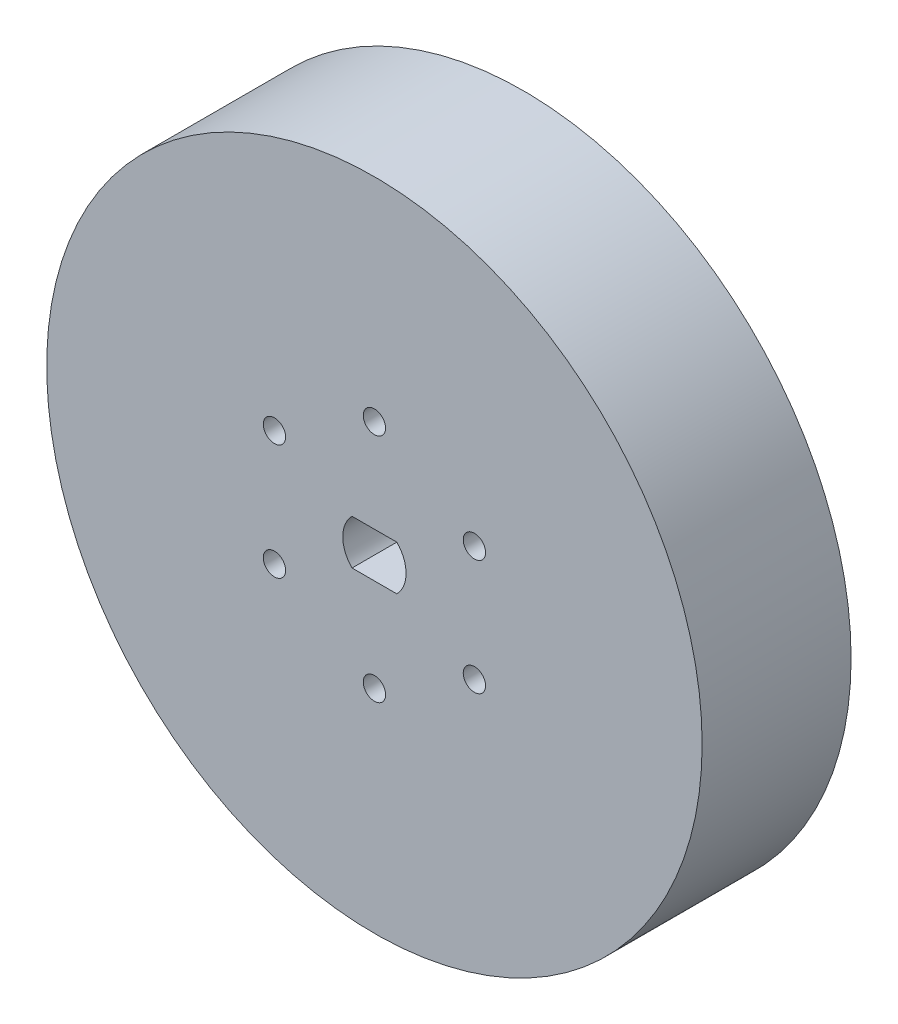
SolidWorks part; units mm, degrees
ref_plane "Front Plane" through (0, 0, 0) normal (0, 0, 1) x (1, 0, 0)
ref_plane "Top Plane" through (0, 0, 0) normal (0, 1, 0) x (1, 0, 0)
ref_plane "Right Plane" through (0, 0, 0) normal (1, 0, 0) x (0, 0, -1)
sketch "Sketch1" plane through (0, 0, 0) normal (0, 0, 1) x (1, 0, 0)
  line L0 (-39.5653, 22.858) -> (-42.5705, 19.8528) construction
  line L7 (-42.5705, 19.8528) -> (-45.5757, 22.858) construction
  line L8 (-39.5653, 22.858) -> (-45.5757, 22.858)
  line L9 (-42.5705, 19.8528) -> (-42.5705, 25.8632) construction
  line L10 (-45.5757, 28.8684) -> (-39.5653, 28.8684)
  line L11 (-42.5705, 28.8684) -> (-42.5705, 30.1132) construction
  circle A0 centre (-42.5705, 25.8632) radius 44
  circle A1 centre (-42.5705, 25.8632) radius 4.25
  dimension "D1" = 45
  dimension "D2" = 1.2448
  dimension "WheelOD" = 88
  dimension "ShaftMajorDiameter" = 8.5
extrude "Boss-Extrude1" add sketch "Sketch1" along normal blind 20 contours A0 A1 | L10 A1 | L8 A1 region at (-42.5705, 22.3532, 0) region at (-42.5705, 29.3732, 0) region at (-85.326, 25.8632, 0)
ref_plane "Plane1" through (0, 0, 0) normal (0, 0, -1) x (-1, 0, 0)
sketch "Sketch2" plane through (0, 0, 0) normal (0, 0, -1) x (-1, 0, 0)
  circle A0 centre (42.5705, 41.3632) radius 3
  circle A1 centre (42.5705, 41.3632) radius 1.5
  point P3 (0, 0)
  dimension "D1" = 6
  dimension "D2" = 3
  dimension "D3" = 15.5
extrude "Cut-Extrude1" cut sketch "Sketch2" against normal through all contours A1
extrude "Cut-Extrude2" cut sketch "Sketch2<3>" against normal blind 3 contours A0
sketch "Sketch2<3>" plane through (0, 0, 0) normal (0, 0, -1) x (-1, 0, 0) same geometry as "Sketch2"
ref_plane "Plane2" through (0, 0, 10) normal (0, 0, -1) x (-1, 0, 0)
pattern_circular "CirPattern1" count 6 over 360 about axis through (-42.5705, 25.8632, 20) along (0, 0, 1) of "Cut-Extrude1", "Cut-Extrude2"
equation "\"WheelOD\"= 88"
equation "\"WheelOR\"= \"WheelOD\" / 2"
equation "\"WheelThickness\"= 20"
equation "\"ShaftMajorDiameter\"= 8 + 0.5"
